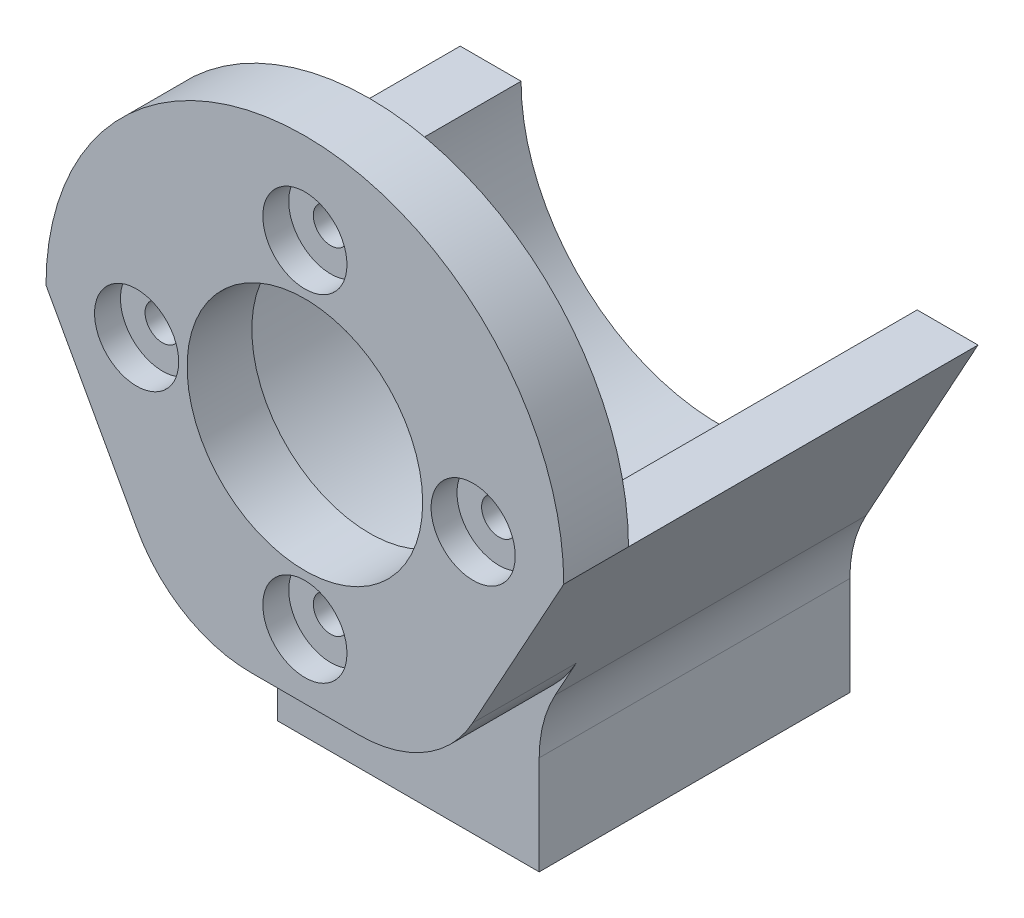
SolidWorks part; units mm, degrees
note: '?' marks a value the reader was unsure of.
ref_plane "Front Plane" through (0, 0, 0) normal (0, 0, 1) x (1, 0, 0)
ref_plane "Top Plane" through (0, 0, 0) normal (0, 1, 0) x (1, 0, 0)
ref_plane "Right Plane" through (0, 0, 0) normal (1, 0, 0) x (0, 0, -1)
ref_axis "Axis1" through (0, 0, -1.4) along (0, 0, 1)?
sketch "Sketch1" plane through (0, 0, 0) normal (0, 0, 1) x (1, 0, 0)
  line L0 (-5.1, -18) -> (-1.45, -18)
  line L1 (-1.45, -18) -> (-1.45, -19)
  line L2 (-1.45, -19) -> (1.45, -19)
  line L3 (1.45, -19) -> (1.45, -18)
  line L4 (1.45, -18) -> (5.1, -18)
  line L5 (5.1, -18) -> (5.1, -21.65)
  line L6 (-5.1, -18) -> (-5.1, -21.65)
  line L7 (-5.1, -21.65) -> (-4.1, -21.65)
  line L8 (-4.1, -21.65) -> (-4.1, -24.55)
  line L9 (-4.1, -24.55) -> (-5.1, -24.55)
  line L10 (-5.1, -24.55) -> (-5.1, -28.2)
  line L11 (-5.1, -28.2) -> (-10.1, -28.2)
  line L12 (-10.1, -18) -> (-20, 0)
  line L13 (5.1, -21.65) -> (4.1, -21.65)
  line L14 (4.1, -21.65) -> (4.1, -24.55)
  line L15 (4.1, -24.55) -> (5.1, -24.55)
  line L16 (5.1, -24.55) -> (5.1, -28.2)
  line L17 (5.1, -28.2) -> (10.1, -28.2)
  line L18 (10.1, -28.2) -> (10.1, -18)
  line L19 (5.1, -15) -> (-5.1, -15) construction
  line L20 (5.1, -18) -> (5.1, -15) construction
  line L21 (-5.1, -18) -> (-5.1, -15) construction
  line L22 (-10.1, -28.2) -> (-10.1, -18)
  line L23 (10.1, -18) -> (20, 0)
  arc A0 (-20, 0) -> (20, 0) centre (0, 0) cw
  circle A1 centre (0, 0) radius 9.1
  point P17 (0, -19)
  dimension "D1" = 20
  dimension "D9" = 18.2
  dimension "D2" = 1
  dimension "D3" = 2.9
  dimension "D4" = 3.65
  dimension "D5" = 10.2
  dimension "D6" = 15
  dimension "D7" = 3
  dimension "D8" = 5
extrude "Main" add sketch "Sketch1" along normal blind 32
sketch "Sketch2" plane through (0, 0, 32) normal (0, 0, 1) x (1, 0, 0)
  circle A0 centre (0, 13) radius 1.35
  point P2 (0, 0)
  dimension "D2" = 2.7
  dimension "D1" = 13
extrude "FixHoleMotors" cut sketch "Sketch2" against normal through all
pattern_circular "HoleCircularPattern" count 4 every 90 about axis through (0, 0, 0) along (0, 0, 1) of "FixHoleMotors"
sketch "Sketch3" plane through (0, 0, 0) normal (0, 0, 1) x (1, 0, 0)
  circle A0 centre (0, 0) radius 15.3
  dimension "D1" = 30.6
extrude "MotorMainHole" cut sketch "Sketch3" along normal blind 27
sketch "Sketch4" plane through (0, 0, 0) normal (0, 0, -1) x (-1, 0, 0)
  line L1 (-20, 0) -> (20, 0)
  line L2 (-20, 0) -> (-20, 20)
  line L3 (-20, 20) -> (20, 20)
  line L4 (20, 0) -> (20, 20)
  arc A0 (20, 0) -> (-20, 0) centre (0, 0) ccw construction
  point P5 (20, 0)
extrude "Cut-Extrude3" cut sketch "Sketch4" against normal up to surface (27 mm away) up to face at (9.1, 0, 27)
sketch "Sketch5" plane through (0, 0, 32) normal (0, 0, 1) x (1, 0, 0)
  circle A0 centre (0, 13) radius 3.25
  circle A1 centre (13, 0) radius 3.25
  circle A2 centre (0, -13) radius 3.25
  circle A3 centre (-13, 0) radius 3.25
  point P11 (0, 13)
  dimension "D1" = 6.5
extrude "HeadScrewHole" cut sketch "Sketch5" against normal blind 2
sketch "Sketch6" plane through (0, 0, 32) normal (0, 0, 1) x (1, 0, 0)
  line L1 (-10.1, -28.2) -> (10.1, -28.2)
  line L2 (-10.1, -28.2) -> (-10.1, -18)
  line L3 (-10.1, -18) -> (10.1, -18)
  line L4 (10.1, -28.2) -> (10.1, -18)
extrude "WheelCut" cut sketch "Sketch6" against normal blind 10
sketch "Sketch7" plane through (0, 0, 22) normal (0, 0, 1) x (1, 0, 0)
  line L1 (-10.1, -28.2) -> (10.1, -28.2)
  line L2 (-10.1, -28.2) -> (-10.1, -18)
  line L3 (-10.1, -18) -> (10.1, -18)
  line L4 (10.1, -28.2) -> (10.1, -18)
  circle A0 centre (0, -23.15) radius 1.6
  point P8 (0, 0)
  dimension "D1" = 3.2
  dimension "D2" = 5.05
extrude "Boss-Extrude2" add sketch "Sketch7" along normal blind 2
fillet "Fillet1" radius 10 2 edges at (-10.1, -18, 28) (10.1, -18, 28)
fillet "Fillet2" radius 10 2 edges at (-10.1, -18, 12) (10.1, -18, 12)
